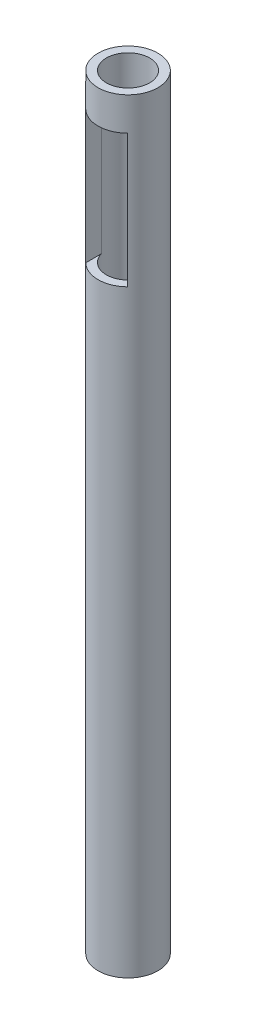
SolidWorks part; units mm, degrees
note: '?' marks a value the reader was unsure of.
material "Plain Carbon Steel"
ref_plane "Front Plane" through (0, 0, 0) normal (0, 0, 1) x (1, 0, 0)
ref_plane "Top Plane" through (0, 0, 0) normal (0, 1, 0) x (1, 0, 0)
ref_plane "Right Plane" through (0, 0, 0) normal (1, 0, 0) x (0, 0, -1)
sketch "Sketch1" plane through (0, 0, 0) normal (0, 1, 0) x (1, 0, 0)
  circle A0 centre (0, 0) radius 13
  circle A1 centre (0, 0) radius 18
  dimension "D1" = 26
  dimension "D2" = 36
extrude "Boss-Extrude1" add sketch "Sketch1" along normal mid plane 450
sketch "Sketch5" plane through (0, 0, 0) normal (1, 0, 0) x (0, 0, -1)
  line L1 (12.407, 241.5319) -> (-12.593, 241.5319)
  line L2 (12.407, 241.5319) -> (12.407, 201.5319)
  line L3 (12.407, 201.5319) -> (-12.593, 201.5319)
  line L4 (-12.593, 241.5319) -> (-12.593, 201.5319)
  dimension "D1" = 40
  dimension "D2" = 25
ref_axis "Axis1" through (0, 225, 0) along (0, -1, 0)?
sketch "Sketch8" plane through (0, -225, 0) normal (0, -1, 0) x (1, 0, 0)
  circle A1 centre (0, 0) radius 18
  circle A2 centre (0, 0) radius 18
  dimension "D1" = 0
extrude "Boss-Extrude3" add sketch "Sketch8" along normal blind 10
extrude "Cut-Extrude2" cut sketch "Sketch9" against normal blind 899.5
sketch "Sketch9" plane through (-32.3028, 416.2892, -45.2219) normal (0, 1, 0) x (-0.9769, 0, 0.2137)
  circle A0 centre (-21.8901, 51.0814) radius 12.55
extrude "Cut-Extrude3" [suppressed] cut sketch "Sketch10" against normal blind 5
sketch "Sketch10" plane through (-25.1589, 226, 55.5571) normal (0, -1, 0) x (0.9695, 0, -0.2452)
  line L5 (60.7638, -17.1919) -> (15.2638, -17.1919)
  line L21 (8.2638, -37.1919) -> (13.2638, -37.1919)
  line L23 (62.7638, -27.1919) -> (62.7638, -19.1919)
  line L25 (62.7638, -76.1919) -> (62.7638, -68.1919)
  line L28 (13.2638, -37.1919) -> (13.2638, -58.1919)
  line L33 (13.2638, -58.1919) -> (8.2638, -58.1919)
  line L37 (8.2638, -58.1919) -> (8.2638, -68.1919)
  line L50 (15.2638, -78.1919) -> (60.7638, -78.1919)
  line L59 (8.2638, -68.1919) -> (13.2638, -68.1919)
  line L61 (13.2638, -68.1919) -> (13.2638, -76.1919)
  line L63 (62.7638, -68.1919) -> (67.7638, -68.1919)
  line L65 (67.7638, -68.1919) -> (67.7638, -58.1919)
  line L67 (67.7638, -58.1919) -> (62.7638, -58.1919)
  line L69 (62.7638, -58.1919) -> (62.7638, -37.1919)
  line L71 (62.7638, -37.1919) -> (67.7638, -37.1919)
  line L73 (67.7638, -37.1919) -> (67.7638, -27.1919)
  line L75 (67.7638, -27.1919) -> (62.7638, -27.1919)
  line L77 (13.2638, -19.1919) -> (13.2638, -27.1919)
  line L79 (13.2638, -27.1919) -> (8.2638, -27.1919)
  line L81 (8.2638, -27.1919) -> (8.2638, -37.1919)
  arc A5 (13.2638, -76.1919) -> (15.2638, -78.1919) centre (15.2638, -76.1919) ccw
  arc A7 (60.7638, -78.1919) -> (62.7638, -76.1919) centre (60.7638, -76.1919) ccw
  arc A29 (15.2638, -17.1919) -> (13.2638, -19.1919) centre (15.2638, -19.1919) ccw
  arc A35 (62.7638, -19.1919) -> (60.7638, -17.1919) centre (60.7638, -19.1919) ccw
extrude "Cut-Extrude15" [suppressed] cut sketch "Sketch22" against normal blind 5
sketch "Sketch22" plane through (-1.1585, 160, -13.857) normal (0, -1, 0) x (-0.2452, 0, -0.9695)
  line L41 (-38.7181, -7.1919) -> (-38.7181, -17.6919)
  line L42 (-38.7181, -17.6919) -> (-42.7181, -17.6919)
  line L43 (-43.7181, -18.6919) -> (-43.7181, -26.6919)
  line L44 (-42.7181, -27.6919) -> (-38.7181, -27.6919)
  line L45 (-38.7181, -27.6919) -> (-38.7181, -67.6919)
  line L46 (-38.7181, -67.6919) -> (-42.7181, -67.6919)
  line L47 (-43.7181, -68.6919) -> (-43.7181, -76.6919)
  line L48 (-42.7181, -77.6919) -> (-38.7181, -77.6919)
  line L49 (-38.7181, -77.6919) -> (-38.7181, -88.1919)
  line L50 (-36.7181, -90.1919) -> (9.2819, -90.1919)
  line L51 (11.2819, -88.1919) -> (11.2819, -77.6919)
  line L52 (11.2819, -77.6919) -> (15.2819, -77.6919)
  line L53 (16.2819, -76.6919) -> (16.2819, -68.6919)
  line L54 (15.2819, -67.6919) -> (11.2819, -67.6919)
  line L55 (11.2819, -67.6919) -> (11.2819, -27.6919)
  line L56 (11.2819, -27.6919) -> (15.2819, -27.6919)
  line L57 (16.2819, -26.6919) -> (16.2819, -18.6919)
  line L58 (15.2819, -17.6919) -> (11.2819, -17.6919)
  line L59 (11.2819, -17.6919) -> (11.2819, -7.1919)
  line L64 (-4.7181, -5.1919) -> (-4.7181, -10.6919)
  line L66 (-6.7181, -12.6919) -> (-20.7181, -12.6919)
  line L68 (-22.7181, -10.6919) -> (-22.7181, -5.1919)
  line L70 (-22.7181, -5.1919) -> (-36.7181, -5.1919)
  line L72 (9.2819, -5.1919) -> (-4.7181, -5.1919)
  arc A16 (-42.7181, -17.6919) -> (-43.7181, -18.6919) centre (-42.7181, -18.6919) ccw
  arc A17 (-43.7181, -26.6919) -> (-42.7181, -27.6919) centre (-42.7181, -26.6919) ccw
  arc A18 (-42.7181, -67.6919) -> (-43.7181, -68.6919) centre (-42.7181, -68.6919) ccw
  arc A19 (-43.7181, -76.6919) -> (-42.7181, -77.6919) centre (-42.7181, -76.6919) ccw
  arc A20 (15.2819, -77.6919) -> (16.2819, -76.6919) centre (15.2819, -76.6919) ccw
  arc A21 (16.2819, -68.6919) -> (15.2819, -67.6919) centre (15.2819, -68.6919) ccw
  arc A22 (15.2819, -27.6919) -> (16.2819, -26.6919) centre (15.2819, -26.6919) ccw
  arc A23 (16.2819, -18.6919) -> (15.2819, -17.6919) centre (15.2819, -18.6919) ccw
  arc A29 (-36.7181, -5.1919) -> (-38.7181, -7.1919) centre (-36.7181, -7.1919) ccw
  arc A31 (-38.7181, -88.1919) -> (-36.7181, -90.1919) centre (-36.7181, -88.1919) ccw
  arc A33 (9.2819, -90.1919) -> (11.2819, -88.1919) centre (9.2819, -88.1919) ccw
  arc A35 (11.2819, -7.1919) -> (9.2819, -5.1919) centre (9.2819, -7.1919) ccw
  arc A39 (-6.7181, -12.6919) -> (-4.7181, -10.6919) centre (-6.7181, -10.6919) ccw
  arc A41 (-22.7181, -10.6919) -> (-20.7181, -12.6919) centre (-20.7181, -10.6919) ccw
sketch "Sketch23" plane through (0, 0, 0) normal (0, 0, 1) x (1, 0, 0)
  line L6 (-12.5, 125) -> (12.5, 125)
  line L7 (0, -19.25) -> (0, 19.25) construction
  line L11 (-12.5, 125) -> (-12.5, 205)
  line L12 (-12.5, 205) -> (12.5, 205)
  line L13 (12.5, 125) -> (12.5, 205)
  line L14 (-12.5, 125) -> (12.5, 205) construction
  line L15 (-12.5, 205) -> (12.5, 125) construction
  line L16 (18, 225) -> (-18, 225) construction
  point P2 (0, 165)
  dimension "D4" = 80
  dimension "D5" = 25
  dimension "D6" = 60
extrude "Cut-Extrude16" cut sketch "Sketch23" along normal blind 30
